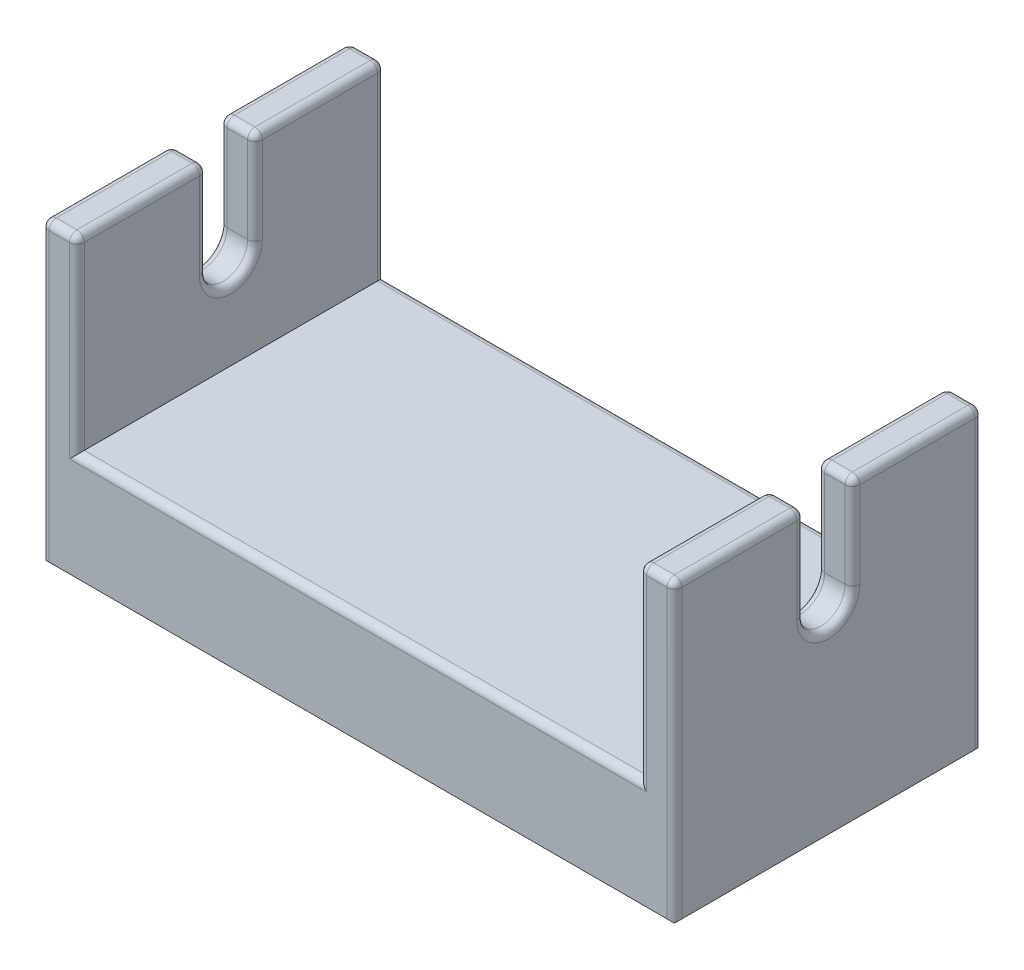
SolidWorks part; units mm, degrees
ref_plane "Front Plane" through (0, 0, 0) normal (0, 0, 1) x (1, 0, 0)
ref_plane "Top Plane" through (0, 0, 0) normal (0, 1, 0) x (1, 0, 0)
ref_plane "Right Plane" through (0, 0, 0) normal (1, 0, 0) x (0, 0, -1)
sketch "Sketch2" plane through (0, 34, 0) normal (0, -1, 0) x (-1, 0, 0)
  line L0 (-150, -197.8) -> (-150, 107) construction
  line L1 (-152.164, -197.8) -> (-147.836, -197.8) construction
  line L2 (-300, 107) -> (0, 107) construction
  line L4 (-107.1248, 0) -> (-192.8752, 0)
  line L5 (-107.1248, 0) -> (-107.1248, -41.7256)
  line L6 (-107.1248, -41.7256) -> (-192.8752, -41.7256)
  line L7 (-192.8752, 0) -> (-192.8752, -41.7256)
  line L8 (-107.1248, 0) -> (-192.8752, -41.7256) construction
  line L9 (-107.1248, -41.7256) -> (-192.8752, 0) construction
  line L10 (-300, 0) -> (0, 0) construction
  line L11 (-188.1, -41.7256) -> (-188.1, 0)
  line L12 (-111.9, -41.7256) -> (-111.9, 0)
  line L13 (-107.1248, -10) -> (-192.8752, -10)
  point P6 (-150, -20.8628)
  dimension "D1" = 10
extrude "Boss-Extrude1" add sketch "Sketch2" along normal blind 15 contours L6 L7 L4 L5
extrude "Boss-Extrude2" add sketch "Sketch2<3>" against normal blind 25.4 contours L5 L13 L12 L6 | L13 L5 L4 L12 | L11 L13 L7 L6 | L13 L11 L4 L7 region at (109.5124, 34, 5) region at (109.5124, 34, 25.8628) region at (190.4876, 34, 5) region at (190.4876, 34, 25.8628)
sketch "Sketch2<3>" plane through (0, 34, 0) normal (0, -1, 0) x (-1, 0, 0) same geometry as "Sketch2"
sketch "Sketch3" plane through (192.8752, 0, 0) normal (1, 0, 0) x (0, 0, -1)
  line L0 (107, 46.7) -> (-41.7256, 46.7) construction
  line L1 (107, 48.864) -> (107, 44.536) construction
  line L2 (-41.7256, 19) -> (-41.7256, 59.4) construction
  line L3 (-24.1267, 46.7) -> (-24.1267, 59.4)
  line L4 (-24.1267, 59.4) -> (-17.5989, 59.4)
  line L5 (-17.5989, 59.4) -> (-17.5989, 46.7)
  line L6 (0, 59.4) -> (-41.7256, 59.4) construction
  line L7 (-24.1267, 59.4) -> (-41.7256, 59.4) construction
  line L8 (-17.5989, 59.4) -> (0, 59.4) construction
  arc A0 (-17.5989, 46.7) -> (-24.1267, 46.7) centre (-20.8628, 46.7) cw
  dimension "D1" = 3.2639
extrude "Cut-Extrude1" cut sketch "Sketch3" against normal through all
chamfer "Chamfer1" distance 0.5 angle 45 4 edges at (150, 19, 41.7256) (192.8752, 19, 20.8628) (150, 19, 0) (107.1248, 19, 20.8628)
fillet "Fillet2" radius 1 38 edges at (111.9, 53.05, 17.5989) (111.9, 43.4361, 20.8628) (107.1248, 53.05, 17.5989) (107.1248, 43.4361, 20.8628) (192.8752, 53.05, 17.5989) (192.8752, 43.4361, 20.8628) (188.1, 53.05, 17.5989) (188.1, 43.4361, 20.8628) (109.5124, 59.4, 0) (111.9, 59.4, 8.7995) (109.5124, 59.4, 17.5989) (107.1248, 59.4, 8.7995) (109.5124, 59.4, 41.7256) (107.1248, 59.4, 32.9262) (111.9, 59.4, 32.9262) (190.4876, 59.4, 0) (192.8752, 59.4, 8.7995) (190.4876, 59.4, 17.5989) (188.1, 59.4, 8.7995) (190.4876, 59.4, 41.7256) (188.1, 59.4, 32.9262) (192.8752, 59.4, 32.9262) (111.9, 53.05, 24.1267) (109.5124, 59.4, 24.1267) (107.1248, 53.05, 24.1267) (192.8752, 53.05, 24.1267) (190.4876, 59.4, 24.1267) (188.1, 53.05, 24.1267) (150, 34, 41.7256) (107.1248, 39.45, 41.7256) (188.1, 46.7, 41.7256) (111.9, 46.7, 41.7256) (192.8752, 39.45, 41.7256) (107.1248, 39.45, 0) (192.8752, 39.45, 0) (188.1, 46.7, 0) (150, 34, 0) (111.9, 46.7, 0)
